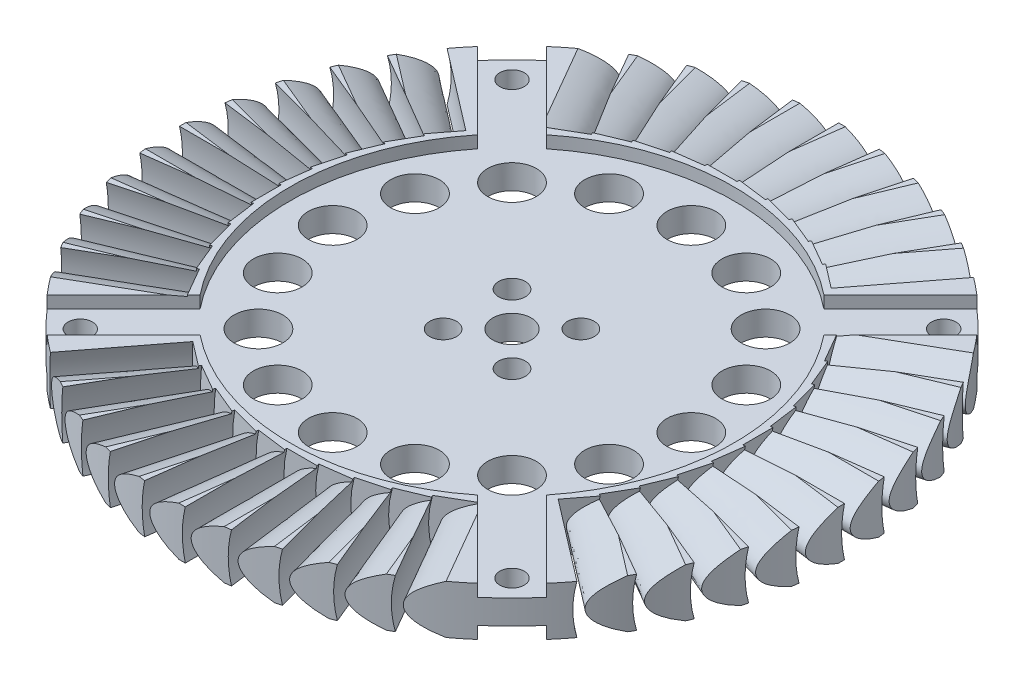
SolidWorks part; units mm, degrees
material "AISI 316 Stainless Steel Sheet (SS)"
ref_plane "Front Plane" through (0, 0, 0) normal (0, 0, 1) x (1, 0, 0)
ref_plane "Top Plane" through (0, 0, 0) normal (0, 1, 0) x (1, 0, 0)
ref_plane "Right Plane" through (0, 0, 0) normal (1, 0, 0) x (0, 0, -1)
ref_axis "Axis1" through (0, 11.1262, 0) along (0, -1, 0)
sketch "Sketch3" plane through (0, 0, 0) normal (0, 0, 1) x (1, 0, 0)
  line L1 (5, -3.175) -> (57.8739, -3.175)
  line L2 (57.8739, -3.175) -> (57.8739, -6.35)
  line L3 (57.8739, -6.35) -> (85.9536, -6.35)
  line L4 (85.9536, -6.35) -> (85.9536, 6.35)
  line L5 (85.9536, 6.35) -> (57.8739, 6.35)
  line L6 (57.8739, 6.35) -> (57.8739, 3.175)
  line L7 (57.8739, 3.175) -> (5, 3.175)
  line L8 (59.4614, 6.35) -> (59.4614, -6.35) construction
  line L9 (5, -3.175) -> (5, 3.175)
  line L10 (0, -10.1148) -> (0, 10.1148) construction
  point P11 (0, 0)
  point P12 (5, 0)
  dimension "D3" = 6.35
  dimension "D4" = 12.7
  dimension "D5" = 1.5875
  dimension "D1" = 5
  dimension "D2" = 59.4614
  dimension "D6" = 85.9536
revolve "Revolve1" add sketch "Sketch3" angle 360 about L10
ref_plane "Blade Plane" through (85.9536, 0, 0) normal (1, 0, 0) x (0, 0, -1)
sketch "Sketch2" plane through (85.9536, 0, 0) normal (1, 0, 0) x (0, 0, -1)
  line L0 (0.7572, 6.35) -> (1.586, 9.7758) construction
  line L1 (0.7572, -6.35) -> (0.7572, 6.35) construction
  line L2 (0.7572, 6.35) -> (10.2729, 6.35)
  line L3 (0.7572, -6.35) -> (10.2729, -6.35)
  line L4 (-7.2551, 0) -> (0, 0) construction
  arc A0 (0.7572, 6.35) -> (0.7572, -6.35) centre (27.0049, 0) ccw
  ellipse E0 centre (43.5449, 0) end of major axis (-7.2551, 0) minor radius 11.7801 (0.7572, -6.35) -> (0.7572, 6.35) cw construction
  ellipse E1 centre (53.0606, 0) end of major axis (2.2606, 0) minor radius 11.7801 (10.2729, -6.35) -> (10.2729, 6.35) cw
  point P5 (0, 0)
  dimension "D1" = 13.6
  dimension "D2" = 12.7
  dimension "D3" = 2.2606
  dimension "D5" = 9.5157
  dimension "D6" = 50.8
extrude "Blade Cut" cut sketch "Sketch2" against normal up to vertex (26.4922 mm away) up to point (59.4614, 6.35, 0)
pattern_circular "CirPattern1" count 48 over 360 about axis through (0, -10.1148, 0) along (0, -1, 0) skipping 5, 6, 17, 18, 29, 30, 41, 42 of "Blade Cut" reverse direction yes
sketch "Sketch4" plane through (0, 3.175, 0) normal (0, 1, 0) x (1, 0, 0)
  line L0 (0, 0) -> (46.7614, 0) construction
  circle A0 centre (46.7614, 0) radius 6.35
  dimension "D2" = 12.7
  dimension "D1" = 46.7614
extrude "Inco Pin Hole" cut sketch "Sketch4" against normal through all
pattern_circular "CirPattern2" count 16 over 360 about axis through (0, 11.1262, 0) along (0, -1, 0) of "Inco Pin Hole"
ref_plane "Plane2" through (0, 0, 0) normal (-0.7071, 0, 0.7071) x (0, -1, 0)
ref_plane "Plane3" through (0, 0, 0) normal (-0.7071, 0, -0.7071) x (0, -1, 0)
sketch "Sketch5" plane through (0, 6.35, 0) normal (0, 1, 0) x (1, 0, 0)
  line L0 (-75.4342, -75.4342) -> (75.4342, 75.4342) construction
  line L1 (-75.4342, 75.4342) -> (75.4342, -75.4342) construction
  line L2 (-79.9243, 70.944) -> (-70.944, 79.9243)
  line L3 (-70.944, 79.9243) -> (79.9243, -70.944)
  line L4 (79.9243, -70.944) -> (70.944, -79.9243)
  line L5 (70.944, -79.9243) -> (-79.9243, 70.944)
  line L6 (70.944, 79.9243) -> (79.9243, 70.944)
  line L7 (79.9243, 70.944) -> (-70.944, -79.9243)
  line L8 (-70.944, -79.9243) -> (-79.9243, -70.944)
  line L9 (-79.9243, -70.944) -> (70.944, 79.9243)
  point P4 (0, 0)
  point P14 (-75.4342, 75.4342)
  point P15 (75.4342, -75.4342)
  point P16 (75.4342, 75.4342)
  point P17 (-75.4342, -75.4342)
  dimension "D1" = 213.36
  dimension "D2" = 12.7
extrude "Structural Tabs" cut sketch "Sketch5" against normal blind 3.175 contours L3 L7 L5 L4 | L9 L8 L7 L5 | L5 L9 L3 L2 | L9 L3 L7 L6 region at (-39.9621, 6.35, -39.9621) region at (-39.9621, 6.35, 39.9621) region at (39.9621, 6.35, -39.9621) region at (39.9621, 6.35, 39.9621)
mirror "Mirror1" about plane through (0, 0, 0) normal (0, 1, 0) of "Structural Tabs"
sketch "Sketch6" plane through (0, 3.175, 0) normal (0, 1, 0) x (1, 0, 0)
  line L0 (0, 0) -> (8.9803, 8.9803) construction
  line L1 (0, 0) -> (31.2735, 0) construction
  line L2 (8.9803, 8.9803) -> (56.2882, 56.2882) construction
  circle A0 centre (56.2882, 56.2882) radius 3.175
  circle A1 centre (8.9803, 8.9803) radius 3.4813
  dimension "D2" = 6.35
  dimension "D3" = 79.6036
  dimension "D1" = 12.7
  dimension "D4" = 45
extrude "Cut-Extrude4" cut sketch "Sketch6" against normal through all
pattern_circular "CirPattern3" count 4 over 360 about axis through (0, 11.1262, 0) along (0, -1, 0) of "Cut-Extrude4"
equation "\"D2@Sketch2\"=\"blade width@[TP] [Turb] Turbine.Assembly\""
equation "\"D3@Sketch2\"=\"blade opening@[TP] [Turb] Turbine.Assembly\""
equation "\"D5@Sketch2\"=2*pi*\"rotor pitchline@[TP] [Turb] Turbine.Assembly\"/\"blade number@[TP] [Turb] Turbine.Assembly\""
equation "\"D1@Sketch2\"=\"blade angle@[TP] [Turb] Turbine.Assembly\""
equation "\"D6@Sketch3\"=\"rotor tip@[TP] [Turb] Turbine.Assembly\""
equation "\"D2@Sketch3\"=\"rotor base@[TP] [Turb] Turbine.Assembly\""
equation "\"D1@Sketch4\"=\"rotor base@[TP] [Turb] Turbine.Assembly\"-1/2"
equation "\"D3@Sketch6\"=\"rotor tip@[TP] [Turb] Turbine.Assembly\"-1/4"
